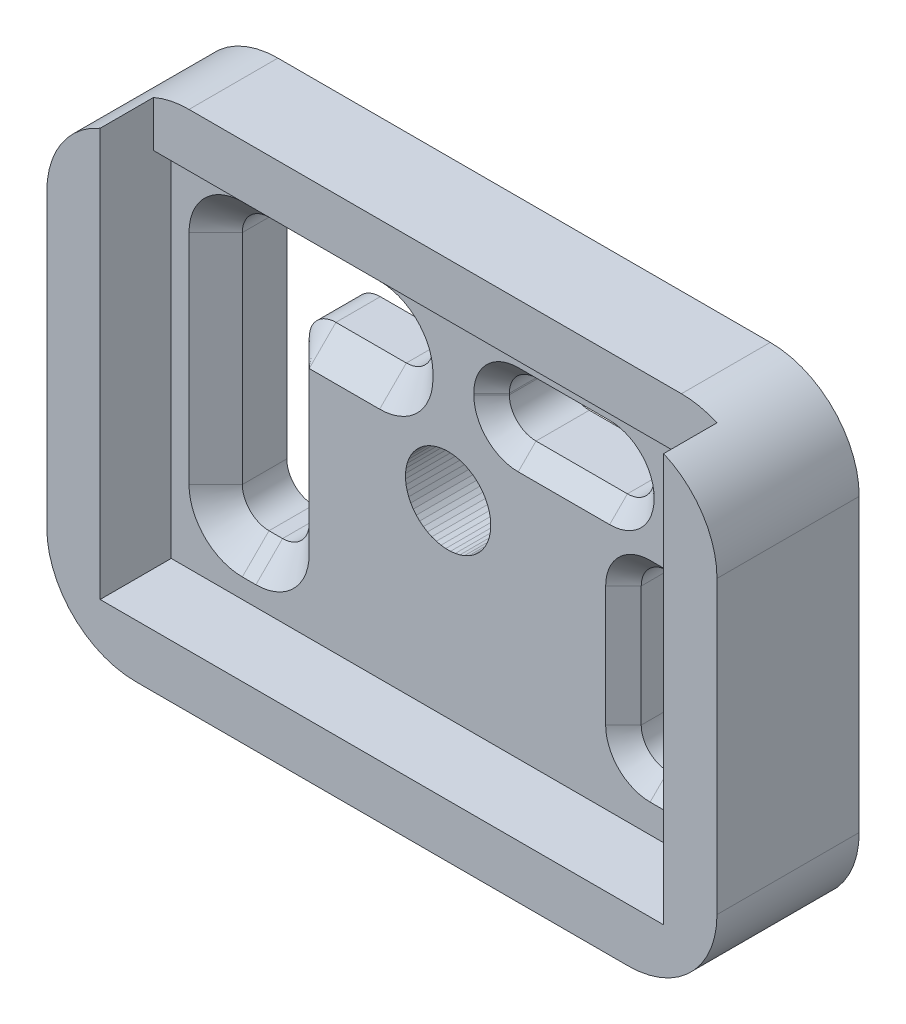
SolidWorks part; units mm, degrees
ref_plane "Alzado" through (0, 0, 0) normal (0, 0, 1) x (1, 0, 0)
ref_plane "Planta" through (0, 0, 0) normal (0, 1, 0) x (1, 0, 0)
ref_plane "Vista lateral" through (0, 0, 0) normal (1, 0, 0) x (0, 0, -1)
sketch "Model" plane through (0, 0, 0) normal (0, 0, 1) x (1, 0, 0)
  line L0 (127.077, -61.2839) -> (127.3394, -61.3438)
  line L1 (127.3394, -61.3438) -> (127.5934, -61.4327)
  line L2 (127.5934, -61.4327) -> (127.8359, -61.5495)
  line L3 (127.8359, -61.5495) -> (128.0638, -61.6927)
  line L4 (128.0638, -61.6927) -> (128.2742, -61.8605)
  line L5 (128.2742, -61.8605) -> (128.4645, -62.0508)
  line L6 (128.4645, -62.0508) -> (128.6323, -62.2612)
  line L7 (128.6323, -62.2612) -> (128.7755, -62.4891)
  line L8 (128.7755, -62.4891) -> (128.8923, -62.7316)
  line L9 (128.8923, -62.7316) -> (128.9812, -62.9856)
  line L10 (128.9812, -62.9856) -> (129.0411, -63.248)
  line L11 (129.0411, -63.248) -> (129.0712, -63.5154)
  line L12 (129.0712, -63.5154) -> (129.0712, -63.7846)
  line L13 (129.0712, -63.7846) -> (129.0411, -64.052)
  line L14 (129.0411, -64.052) -> (128.9812, -64.3144)
  line L15 (128.9812, -64.3144) -> (128.8923, -64.5684)
  line L16 (128.8923, -64.5684) -> (128.7755, -64.8109)
  line L17 (128.7755, -64.8109) -> (128.6323, -65.0388)
  line L18 (128.6323, -65.0388) -> (128.4645, -65.2492)
  line L19 (128.4645, -65.2492) -> (128.2742, -65.4395)
  line L20 (128.2742, -65.4395) -> (128.0638, -65.6073)
  line L21 (128.0638, -65.6073) -> (127.8359, -65.7505)
  line L22 (127.8359, -65.7505) -> (127.5934, -65.8673)
  line L23 (127.5934, -65.8673) -> (127.3394, -65.9562)
  line L24 (127.3394, -65.9562) -> (127.077, -66.0161)
  line L25 (127.077, -66.0161) -> (126.8096, -66.0462)
  line L26 (126.8096, -66.0462) -> (126.5404, -66.0462)
  line L27 (126.5404, -66.0462) -> (126.273, -66.0161)
  line L28 (126.273, -66.0161) -> (126.0106, -65.9562)
  line L29 (126.0106, -65.9562) -> (125.7566, -65.8673)
  line L30 (125.7566, -65.8673) -> (125.5141, -65.7505)
  line L31 (125.5141, -65.7505) -> (125.2862, -65.6073)
  line L32 (125.2862, -65.6073) -> (125.0758, -65.4395)
  line L33 (125.0758, -65.4395) -> (124.8855, -65.2492)
  line L34 (124.8855, -65.2492) -> (124.7177, -65.0388)
  line L35 (124.7177, -65.0388) -> (124.5745, -64.8109)
  line L36 (124.5745, -64.8109) -> (124.4577, -64.5684)
  line L37 (124.4577, -64.5684) -> (124.3688, -64.3144)
  line L38 (124.3688, -64.3144) -> (124.3089, -64.052)
  line L39 (124.3089, -64.052) -> (124.2788, -63.7846)
  line L40 (124.2788, -63.7846) -> (124.2788, -63.5154)
  line L41 (124.2788, -63.5154) -> (124.2799, -63.5058)
  line L42 (124.2799, -63.5058) -> (124.3089, -63.248)
  line L43 (124.3089, -63.248) -> (124.3688, -62.9856)
  line L44 (124.3688, -62.9856) -> (124.4577, -62.7316)
  line L45 (124.4577, -62.7316) -> (124.5745, -62.4891)
  line L46 (124.5745, -62.4891) -> (124.7177, -62.2612)
  line L47 (124.7177, -62.2612) -> (124.8855, -62.0508)
  line L48 (124.8855, -62.0508) -> (125.0758, -61.8605)
  line L49 (125.0758, -61.8605) -> (125.2862, -61.6927)
  line L50 (125.2862, -61.6927) -> (125.5141, -61.5495)
  line L51 (125.5141, -61.5495) -> (125.7566, -61.4327)
  line L52 (125.7566, -61.4327) -> (126.0106, -61.3438)
  line L53 (126.0106, -61.3438) -> (126.273, -61.2839)
  line L54 (126.273, -61.2839) -> (126.5404, -61.2538)
  line L55 (126.5404, -61.2538) -> (126.8096, -61.2538)
  line L56 (126.8096, -61.2538) -> (127.077, -61.2839)
  line L57 (124.475, -63.7942) -> (124.5126, -64.0801)
  line L58 (124.5126, -64.0801) -> (124.5873, -64.3587)
  line L59 (124.5873, -64.3587) -> (124.6976, -64.6251)
  line L60 (124.6976, -64.6251) -> (124.8418, -64.8749)
  line L61 (124.8418, -64.8749) -> (125.0174, -65.1037)
  line L62 (125.0174, -65.1037) -> (125.2213, -65.3076)
  line L63 (125.2213, -65.3076) -> (125.4501, -65.4832)
  line L64 (125.4501, -65.4832) -> (125.6999, -65.6274)
  line L65 (125.6999, -65.6274) -> (125.9663, -65.7377)
  line L66 (125.9663, -65.7377) -> (126.2449, -65.8124)
  line L67 (126.2449, -65.8124) -> (126.5308, -65.85)
  line L68 (126.5308, -65.85) -> (126.8192, -65.85)
  line L69 (126.8192, -65.85) -> (127.1051, -65.8124)
  line L70 (127.1051, -65.8124) -> (127.3837, -65.7377)
  line L71 (127.3837, -65.7377) -> (127.6501, -65.6274)
  line L72 (127.6501, -65.6274) -> (127.8999, -65.4832)
  line L73 (127.8999, -65.4832) -> (128.1287, -65.3076)
  line L74 (128.1287, -65.3076) -> (128.3326, -65.1037)
  line L75 (128.3326, -65.1037) -> (128.5082, -64.8749)
  line L76 (128.5082, -64.8749) -> (128.6524, -64.6251)
  line L77 (128.6524, -64.6251) -> (128.7627, -64.3587)
  line L78 (128.7627, -64.3587) -> (128.8374, -64.0801)
  line L79 (128.8374, -64.0801) -> (128.875, -63.7942)
  line L80 (128.875, -63.7942) -> (128.875, -63.5058)
  line L81 (128.875, -63.5058) -> (128.8374, -63.2199)
  line L82 (128.8374, -63.2199) -> (128.7627, -62.9413)
  line L83 (128.7627, -62.9413) -> (128.6524, -62.6749)
  line L84 (128.6524, -62.6749) -> (128.5082, -62.4251)
  line L85 (128.5082, -62.4251) -> (128.3326, -62.1963)
  line L86 (128.3326, -62.1963) -> (128.1287, -61.9924)
  line L87 (128.1287, -61.9924) -> (127.8999, -61.8168)
  line L88 (127.8999, -61.8168) -> (127.6501, -61.6726)
  line L89 (127.6501, -61.6726) -> (127.3837, -61.5623)
  line L90 (127.3837, -61.5623) -> (127.1051, -61.4876)
  line L91 (127.1051, -61.4876) -> (126.8192, -61.45)
  line L92 (126.8192, -61.45) -> (126.5308, -61.45)
  line L93 (126.5308, -61.45) -> (126.2449, -61.4876)
  line L94 (126.2449, -61.4876) -> (125.9663, -61.5623)
  line L95 (125.9663, -61.5623) -> (125.6999, -61.6726)
  line L96 (125.6999, -61.6726) -> (125.4501, -61.8168)
  line L97 (125.4501, -61.8168) -> (125.2213, -61.9924)
  line L98 (125.2213, -61.9924) -> (125.0174, -62.1963)
  line L99 (125.0174, -62.1963) -> (124.8418, -62.4251)
  line L100 (124.8418, -62.4251) -> (124.6976, -62.6749)
  line L101 (124.6976, -62.6749) -> (124.5873, -62.9413)
  line L102 (124.5873, -62.9413) -> (124.5126, -63.2199)
  line L103 (124.5126, -63.2199) -> (124.475, -63.5058)
  line L104 (124.475, -63.5058) -> (124.475, -63.7942)
  line L105 (142.9195, -53.6769) -> (142.9556, -53.6919)
  line L106 (142.9556, -53.6919) -> (142.9831, -53.7194)
  line L107 (142.9831, -53.7194) -> (142.9981, -53.7555)
  line L108 (142.9981, -53.7555) -> (143, -53.775)
  line L109 (143, -53.775) -> (143, -74.35)
  line L110 (143, -74.35) -> (142.9981, -74.3695)
  line L111 (142.9981, -74.3695) -> (142.9831, -74.4056)
  line L112 (142.9831, -74.4056) -> (142.9556, -74.4331)
  line L113 (142.9556, -74.4331) -> (142.9195, -74.4481)
  line L114 (142.9195, -74.4481) -> (142.9, -74.45)
  line L115 (142.9, -74.45) -> (111, -74.45)
  line L116 (111, -74.45) -> (110.9805, -74.4481)
  line L117 (110.9805, -74.4481) -> (110.9444, -74.4331)
  line L118 (110.9444, -74.4331) -> (110.9169, -74.4056)
  line L119 (110.9169, -74.4056) -> (110.9019, -74.3695)
  line L120 (110.9019, -74.3695) -> (110.9, -74.35)
  line L121 (110.9, -74.35) -> (110.9, -53.775)
  line L122 (110.9, -53.775) -> (110.9019, -53.7555)
  line L123 (110.9019, -53.7555) -> (110.9169, -53.7194)
  line L124 (110.9169, -53.7194) -> (110.9444, -53.6919)
  line L125 (110.9444, -53.6919) -> (110.9805, -53.6769)
  line L126 (110.9805, -53.6769) -> (111, -53.675)
  line L127 (111, -53.675) -> (142.9, -53.675)
  line L128 (142.9, -53.675) -> (142.9195, -53.6769)
  line L129 (111.1, -53.875) -> (111.1, -74.25)
  line L130 (111.1, -74.25) -> (142.8, -74.25)
  line L131 (142.8, -74.25) -> (142.8, -53.875)
  line L132 (142.8, -53.875) -> (111.1, -53.875)
extrude "Saliente-Extruir1" add sketch "Model" along normal blind 4 contours L131 L132 L129 L130 L55 L56 L0 L1 L2 L3 L4 L5 L6 L7 L8 L9 L10 L11 L12 L13 L14 L15 L16 L17 L18 L19 L20 L21 L22 L23 L24 L25 L26 L27 L28 L29 L30 L31 L32 L33 L34 L35 L36 L37 L38 L39 L40 L41 L42 L43 region at (126.95, -54.2518, 0)
sketch "Croquis3" plane through (0, 0, 4) normal (0, 0, 1) x (1, 0, 0)
  line L0 (108.1, -50.875) -> (108.1, -77.25)
  line L1 (108.1, -77.25) -> (145.8, -77.25)
  line L2 (145.8, -77.25) -> (145.8, -50.875)
  line L3 (145.8, -50.875) -> (108.1, -50.875)
  line L4 (142.8, -74.25) -> (142.8, -53.875)
  line L5 (142.8, -53.875) -> (111.1, -53.875)
  line L6 (111.1, -53.875) -> (111.1, -74.25)
  line L7 (111.1, -74.25) -> (142.8, -74.25)
  line L8 (142.8, -74.25) -> (142.8, -53.875)
  line L9 (142.8, -53.875) -> (111.1, -53.875)
  line L10 (111.1, -53.875) -> (111.1, -74.25)
  line L11 (111.1, -74.25) -> (142.8, -74.25)
  dimension "D1" = 0
  dimension "D2" = 3
extrude "Saliente-Extruir2" add sketch "Croquis3" along normal blind 4 and the other way up to surface (4 mm away) other way up to face at (126.633, -63.6475, 0)
fillet "Redondeo1" radius 5 2 edges at (145.8, -77.25, 4) (108.1, -77.25, 4)
fillet "Redondeo3" radius 5 2 edges at (108.1, -50.875, 4) (145.8, -50.875, 4)
sketch "Croquis8" plane through (0, -53.875, 0) normal (0, -1, 0) x (1, 0, 0)
  line L1 (111.1, 8) -> (142.8, 8)
  line L2 (111.1, 8) -> (111.1, 4.9999)
  line L3 (111.1, 4.9999) -> (142.8, 4.9999)
  line L4 (142.8, 8) -> (142.8, 4.9999)
  line L5 (140.8, 0) -> (140.8, 8) construction
  dimension "D1" = 3.0001
  dimension "D2" = 2
extrude "Cortar-Extruir2" cut sketch "Croquis8" against normal blind 4
sketch "Croquis9" plane through (0, 0, 4) normal (0, 0, 1) x (1, 0, 0)
  line L0 (111.1, -53.875) -> (142.8, -53.875) construction
  line L1 (115.1, -56.375) -> (118.626, -56.375)
  line L2 (113.6, -57.875) -> (113.6, -70.15)
  line L3 (115.1, -71.65) -> (115.8626, -71.65)
  line L4 (117.3626, -61.1163) -> (117.3626, -70.15)
  line L5 (111.1, -74.25) -> (142.8, -74.25) construction
  line L6 (111.1, -51.2924) -> (111.1, -74.25) construction
  line L7 (126.95, -53.875) -> (126.95, -74.25) construction
  line L8 (111.1, -74.25) -> (142.8, -74.25) construction
  line L9 (138.8, -71.65) -> (138.0374, -71.65)
  line L10 (136.5374, -63.375) -> (136.5374, -70.15)
  line L11 (138.8, -61.875) -> (138.0374, -61.875)
  line L12 (140.3, -63.375) -> (140.3, -70.15)
  line L14 (130.6189, -56.1941) -> (135.7611, -56.1941)
  line L15 (129.1189, -57.6941) -> (129.1189, -57.7712)
  line L16 (130.6189, -59.2712) -> (135.7611, -59.2712)
  line L17 (137.2611, -57.6941) -> (137.2611, -57.7712)
  line L18 (118.626, -56.375) -> (122.8241, -56.375)
  line L20 (118.8626, -59.6163) -> (122.8241, -59.6163)
  line L21 (124.3241, -57.875) -> (124.3241, -58.1163)
  arc A0 (138.8, -71.65) -> (140.3, -70.15) centre (138.8, -70.15) ccw
  arc A1 (138.0374, -71.65) -> (136.5374, -70.15) centre (138.0374, -70.15) cw
  arc A2 (138.8, -61.875) -> (140.3, -63.375) centre (138.8, -63.375) cw
  arc A3 (136.5374, -63.375) -> (138.0374, -61.875) centre (138.0374, -63.375) cw
  arc A4 (135.7611, -59.2712) -> (137.2611, -57.7712) centre (135.7611, -57.7712) ccw
  arc A5 (135.7611, -56.1941) -> (137.2611, -57.6941) centre (135.7611, -57.6941) cw
  arc A6 (129.1189, -57.7712) -> (130.6189, -59.2712) centre (130.6189, -57.7712) ccw
  arc A7 (130.6189, -56.1941) -> (129.1189, -57.6941) centre (130.6189, -57.6941) ccw
  arc A8 (122.8241, -56.375) -> (124.3241, -57.875) centre (122.8241, -57.875) cw
  arc A9 (122.8241, -59.6163) -> (124.3241, -58.1163) centre (122.8241, -58.1163) ccw
  arc A10 (117.3626, -61.1163) -> (118.8626, -59.6163) centre (118.8626, -61.1163) cw
  arc A11 (115.8626, -71.65) -> (117.3626, -70.15) centre (115.8626, -70.15) ccw
  arc A12 (113.6, -70.15) -> (115.1, -71.65) centre (115.1, -70.15) ccw
  arc A13 (115.1, -56.375) -> (113.6, -57.875) centre (115.1, -57.875) ccw
  point P27 (140.3, -71.65)
  point P30 (136.5374, -71.65)
  point P51 (117.3626, -71.65)
  point P54 (113.6, -71.65)
  dimension "D5" = 1.5
  dimension "D1" = 2.5
  dimension "D2" = 2.6
  dimension "D3" = 2.5
  dimension "D4" = 8
extrude "Cortar-Extruir3" cut sketch "Croquis9" against normal blind 4
chamfer "Chaflán3" distance 1.5 angle 45 12 edges at (114.0393, -71.2107, 4) (115.4813, -71.65, 4) (113.6, -64.0125, 4) (116.9233, -71.2107, 4) (114.0393, -56.8143, 4) (117.3626, -65.6331, 4) (118.962, -56.375, 4) (117.802, -60.0556, 4) (123.8847, -56.8143, 4) (120.8434, -59.6163, 4) (124.3241, -57.9956, 4) (123.8847, -59.1769, 4)
chamfer "Chaflán4" distance 1 angle 45 16 edges at (136.5374, -66.7625, 4) (136.9767, -71.2107, 4) (136.9767, -62.3143, 4) (138.4187, -71.65, 4) (138.4187, -61.875, 4) (139.8607, -71.2107, 4) (139.8607, -62.3143, 4) (140.3, -66.7625, 4) (133.19, -56.1941, 4) (129.5583, -56.6334, 4) (136.8218, -56.6334, 4) (129.1189, -57.7326, 4) (137.2611, -57.7326, 4) (129.5583, -58.8318, 4) (136.8218, -58.8318, 4) (133.19, -59.2712, 4)
